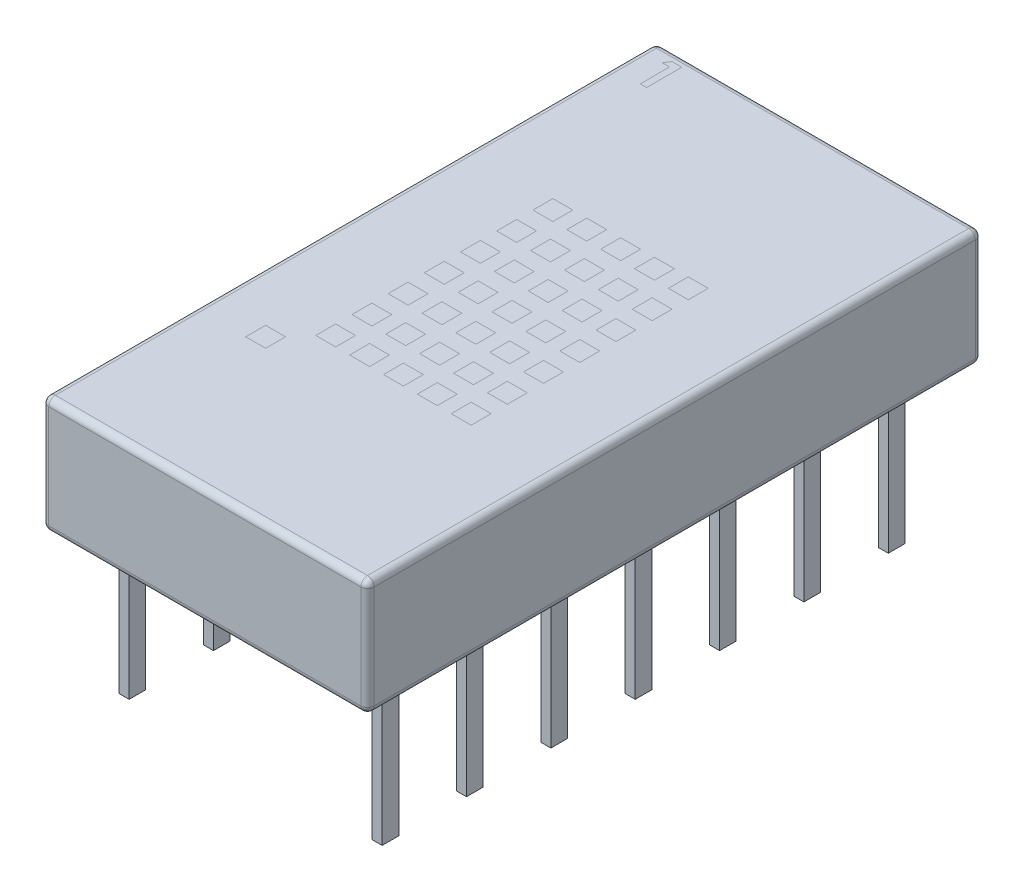
SolidWorks part; units mm, degrees
ref_plane "Front Plane" through (0, 0, 0) normal (0, 0, 1) x (1, 0, 0)
ref_plane "Top Plane" through (0, 0, 0) normal (0, 1, 0) x (1, 0, 0)
ref_plane "Right Plane" through (0, 0, 0) normal (1, 0, 0) x (0, 0, -1)
sketch "Sketch1" plane through (0, 0, 0) normal (0, 1, 0) x (1, 0, 0)
  line L1 (4.9, -9.25) -> (-4.9, -9.25)
  line L2 (4.9, -9.25) -> (4.9, 9.25)
  line L3 (4.9, 9.25) -> (-4.9, 9.25)
  line L4 (-4.9, -9.25) -> (-4.9, 9.25)
  line L5 (4.9, -9.25) -> (-4.9, 9.25) construction
  line L6 (4.9, 9.25) -> (-4.9, -9.25) construction
  point P0 (0, 0)
  dimension "D1" = 9.8
  dimension "D2" = 18.5
extrude "Boss-Extrude1" add sketch "Sketch1" along normal blind 3.5
sketch "Sketch2" plane through (0, 3.5, 0) normal (0, 1, 0) x (1, 0, 0)
  line L0 (0, 9.25) -> (0, 0) construction
  line L1 (4.9, 9.25) -> (-4.9, 9.25) construction
  line L2 (0, 0) -> (4.9, 0) construction
  line L3 (4.9, -9.25) -> (4.9, 9.25) construction
  line L4 (-1.32, 3.57) -> (-0.72, 3.57)
  line L5 (-2.34, 3.57) -> (-1.74, 3.57)
  line L6 (-2.34, 3.57) -> (-2.34, 2.97)
  line L7 (-2.34, 2.97) -> (-1.74, 2.97)
  line L8 (-1.74, 3.57) -> (-1.74, 2.97)
  line L9 (-2.34, 3.57) -> (-1.74, 2.97) construction
  line L10 (-2.34, 2.97) -> (-1.74, 3.57) construction
  line L11 (-0.72, 3.57) -> (-0.72, 2.97)
  line L12 (-1.32, 2.97) -> (-0.72, 2.97)
  line L13 (-1.32, 3.57) -> (-1.32, 2.97)
  line L14 (-0.3, 3.57) -> (0.3, 3.57)
  line L15 (0.3, 3.57) -> (0.3, 2.97)
  line L16 (-0.3, 2.97) -> (0.3, 2.97)
  line L17 (-0.3, 3.57) -> (-0.3, 2.97)
  line L18 (0.72, 3.57) -> (1.32, 3.57)
  line L19 (1.32, 3.57) -> (1.32, 2.97)
  line L20 (0.72, 2.97) -> (1.32, 2.97)
  line L21 (0.72, 3.57) -> (0.72, 2.97)
  line L22 (1.74, 3.57) -> (2.34, 3.57)
  line L23 (2.34, 3.57) -> (2.34, 2.97)
  line L24 (1.74, 2.97) -> (2.34, 2.97)
  line L25 (1.74, 3.57) -> (1.74, 2.97)
  line L26 (-1.32, 2.48) -> (-0.72, 2.48)
  line L27 (-0.72, 2.48) -> (-0.72, 1.88)
  line L28 (-1.32, 1.88) -> (-0.72, 1.88)
  line L29 (-1.32, 2.48) -> (-1.32, 1.88)
  line L30 (-0.3, 2.48) -> (0.3, 2.48)
  line L31 (0.3, 2.48) -> (0.3, 1.88)
  line L32 (-0.3, 1.88) -> (0.3, 1.88)
  line L33 (-0.3, 2.48) -> (-0.3, 1.88)
  line L34 (0.72, 2.48) -> (1.32, 2.48)
  line L35 (1.32, 2.48) -> (1.32, 1.88)
  line L36 (0.72, 1.88) -> (1.32, 1.88)
  line L37 (0.72, 2.48) -> (0.72, 1.88)
  line L38 (1.74, 2.48) -> (2.34, 2.48)
  line L39 (2.34, 2.48) -> (2.34, 1.88)
  line L40 (1.74, 1.88) -> (2.34, 1.88)
  line L41 (1.74, 2.48) -> (1.74, 1.88)
  line L42 (-1.32, 1.39) -> (-0.72, 1.39)
  line L43 (-0.72, 1.39) -> (-0.72, 0.79)
  line L44 (-1.32, 0.79) -> (-0.72, 0.79)
  line L45 (-1.32, 1.39) -> (-1.32, 0.79)
  line L46 (-0.3, 1.39) -> (0.3, 1.39)
  line L47 (0.3, 1.39) -> (0.3, 0.79)
  line L48 (-0.3, 0.79) -> (0.3, 0.79)
  line L49 (-0.3, 1.39) -> (-0.3, 0.79)
  line L50 (0.72, 1.39) -> (1.32, 1.39)
  line L51 (1.32, 1.39) -> (1.32, 0.79)
  line L52 (0.72, 0.79) -> (1.32, 0.79)
  line L53 (0.72, 1.39) -> (0.72, 0.79)
  line L54 (1.74, 1.39) -> (2.34, 1.39)
  line L55 (2.34, 1.39) -> (2.34, 0.79)
  line L56 (1.74, 0.79) -> (2.34, 0.79)
  line L57 (1.74, 1.39) -> (1.74, 0.79)
  line L58 (-1.32, 0.3) -> (-0.72, 0.3)
  line L59 (-0.72, 0.3) -> (-0.72, -0.3)
  line L60 (-1.32, -0.3) -> (-0.72, -0.3)
  line L61 (-1.32, 0.3) -> (-1.32, -0.3)
  line L62 (-0.3, 0.3) -> (0.3, 0.3)
  line L63 (0.3, 0.3) -> (0.3, -0.3)
  line L64 (-0.3, -0.3) -> (0.3, -0.3)
  line L65 (-0.3, 0.3) -> (-0.3, -0.3)
  line L66 (0.72, 0.3) -> (1.32, 0.3)
  line L67 (1.32, 0.3) -> (1.32, -0.3)
  line L68 (0.72, -0.3) -> (1.32, -0.3)
  line L69 (0.72, 0.3) -> (0.72, -0.3)
  line L70 (1.74, 0.3) -> (2.34, 0.3)
  line L71 (2.34, 0.3) -> (2.34, -0.3)
  line L72 (1.74, -0.3) -> (2.34, -0.3)
  line L73 (1.74, 0.3) -> (1.74, -0.3)
  line L74 (-1.32, -0.79) -> (-0.72, -0.79)
  line L75 (-0.72, -0.79) -> (-0.72, -1.39)
  line L76 (-1.32, -1.39) -> (-0.72, -1.39)
  line L77 (-1.32, -0.79) -> (-1.32, -1.39)
  line L78 (-0.3, -0.79) -> (0.3, -0.79)
  line L79 (0.3, -0.79) -> (0.3, -1.39)
  line L80 (-0.3, -1.39) -> (0.3, -1.39)
  line L81 (-0.3, -0.79) -> (-0.3, -1.39)
  line L82 (0.72, -0.79) -> (1.32, -0.79)
  line L83 (1.32, -0.79) -> (1.32, -1.39)
  line L84 (0.72, -1.39) -> (1.32, -1.39)
  line L85 (0.72, -0.79) -> (0.72, -1.39)
  line L86 (1.74, -0.79) -> (2.34, -0.79)
  line L87 (2.34, -0.79) -> (2.34, -1.39)
  line L88 (1.74, -1.39) -> (2.34, -1.39)
  line L89 (1.74, -0.79) -> (1.74, -1.39)
  line L90 (-1.32, -1.88) -> (-0.72, -1.88)
  line L91 (-0.72, -1.88) -> (-0.72, -2.48)
  line L92 (-1.32, -2.48) -> (-0.72, -2.48)
  line L93 (-1.32, -1.88) -> (-1.32, -2.48)
  line L94 (-0.3, -1.88) -> (0.3, -1.88)
  line L95 (0.3, -1.88) -> (0.3, -2.48)
  line L96 (-0.3, -2.48) -> (0.3, -2.48)
  line L97 (-0.3, -1.88) -> (-0.3, -2.48)
  line L98 (0.72, -1.88) -> (1.32, -1.88)
  line L99 (1.32, -1.88) -> (1.32, -2.48)
  line L100 (0.72, -2.48) -> (1.32, -2.48)
  line L101 (0.72, -1.88) -> (0.72, -2.48)
  line L102 (1.74, -1.88) -> (2.34, -1.88)
  line L103 (2.34, -1.88) -> (2.34, -2.48)
  line L104 (1.74, -2.48) -> (2.34, -2.48)
  line L105 (1.74, -1.88) -> (1.74, -2.48)
  line L106 (-1.32, -2.97) -> (-0.72, -2.97)
  line L107 (-0.72, -2.97) -> (-0.72, -3.57)
  line L108 (-1.32, -3.57) -> (-0.72, -3.57)
  line L109 (-1.32, -2.97) -> (-1.32, -3.57)
  line L110 (-0.3, -2.97) -> (0.3, -2.97)
  line L111 (0.3, -2.97) -> (0.3, -3.57)
  line L112 (-0.3, -3.57) -> (0.3, -3.57)
  line L113 (-0.3, -2.97) -> (-0.3, -3.57)
  line L114 (0.72, -2.97) -> (1.32, -2.97)
  line L115 (1.32, -2.97) -> (1.32, -3.57)
  line L116 (0.72, -3.57) -> (1.32, -3.57)
  line L117 (0.72, -2.97) -> (0.72, -3.57)
  line L118 (1.74, -2.97) -> (2.34, -2.97)
  line L119 (2.34, -2.97) -> (2.34, -3.57)
  line L120 (1.74, -3.57) -> (2.34, -3.57)
  line L121 (1.74, -2.97) -> (1.74, -3.57)
  line L122 (-2.34, 2.48) -> (-1.74, 2.48)
  line L123 (-1.74, 2.48) -> (-1.74, 1.88)
  line L124 (-2.34, 1.88) -> (-1.74, 1.88)
  line L125 (-2.34, 2.48) -> (-2.34, 1.88)
  line L126 (-2.34, 1.39) -> (-1.74, 1.39)
  line L127 (-1.74, 1.39) -> (-1.74, 0.79)
  line L128 (-2.34, 0.79) -> (-1.74, 0.79)
  line L129 (-2.34, 1.39) -> (-2.34, 0.79)
  line L130 (-2.34, 0.3) -> (-1.74, 0.3)
  line L131 (-1.74, 0.3) -> (-1.74, -0.3)
  line L132 (-2.34, -0.3) -> (-1.74, -0.3)
  line L133 (-2.34, 0.3) -> (-2.34, -0.3)
  line L134 (-2.34, -0.79) -> (-1.74, -0.79)
  line L135 (-1.74, -0.79) -> (-1.74, -1.39)
  line L136 (-2.34, -1.39) -> (-1.74, -1.39)
  line L137 (-2.34, -0.79) -> (-2.34, -1.39)
  line L138 (-2.34, -1.88) -> (-1.74, -1.88)
  line L139 (-1.74, -1.88) -> (-1.74, -2.48)
  line L140 (-2.34, -2.48) -> (-1.74, -2.48)
  line L141 (-2.34, -1.88) -> (-2.34, -2.48)
  line L142 (-2.34, -2.97) -> (-1.74, -2.97)
  line L143 (-1.74, -2.97) -> (-1.74, -3.57)
  line L144 (-2.34, -3.57) -> (-1.74, -3.57)
  line L145 (-2.34, -2.97) -> (-2.34, -3.57)
  line L146 (-2.34, 3.57) -> (-1.32, 3.57) construction
  line L147 (-2.34, 3.57) -> (-2.34, 2.48) construction
  line L148 (-0.3, 0.3) -> (0.3, -0.3) construction
  line L149 (-1.74, -2.97) -> (-1.32, -2.97) construction
  line L150 (-3.36, -4.06) -> (-2.76, -4.06)
  line L151 (-3.36, -4.06) -> (-3.36, -4.66)
  line L152 (-3.36, -4.66) -> (-2.76, -4.66)
  line L153 (-2.76, -4.06) -> (-2.76, -4.66)
  line L154 (-3.36, -4.06) -> (-2.76, -4.66) construction
  line L155 (-3.36, -4.66) -> (-2.76, -4.06) construction
  line L156 (-1.74, -2.48) -> (-1.74, -2.97) construction
  line L157 (-2.34, -3.57) -> (-2.34, -4.06) construction
  line L158 (-2.34, -4.06) -> (-2.76, -4.06) construction
  text T0 "<b>1</b>" font "Century Gothic" height in points 4
  point P5 (-2.04, 3.27)
  point P13 (0, 0)
  point P14 (-3.06, -4.36)
  dimension "D1" = 0.6
  dimension "D2" = 0.6
  dimension "D5" = 90
  dimension "D6" = 1.02
  dimension "D7" = 1.09
  dimension "D3" = 5
  dimension "D4" = 7
wrap "Wrap1" sketch "Sketch2" wrap type scribe source sketch "Sketch2"
sketch "Sketch3" plane through (0, 0, 0) normal (0, -1, 0) x (1, 0, 0)
  line L0 (3.96, -7.87) -> (3.96, -7.37)
  line L1 (-3.66, -7.87) -> (-3.96, -7.87)
  line L2 (-3.66, -7.87) -> (-3.66, -7.37)
  line L3 (-3.66, -7.37) -> (-3.96, -7.37)
  line L4 (-3.96, -7.87) -> (-3.96, -7.37)
  line L5 (-3.66, -7.87) -> (-3.96, -7.37) construction
  line L6 (-3.66, -7.37) -> (-3.96, -7.87) construction
  line L7 (3.96, -7.87) -> (3.66, -7.87)
  line L8 (3.66, -7.87) -> (3.66, -7.37)
  line L9 (3.96, -7.37) -> (3.66, -7.37)
  line L10 (3.96, -5.33) -> (3.96, -4.83)
  line L11 (3.96, -5.33) -> (3.66, -5.33)
  line L12 (3.66, -5.33) -> (3.66, -4.83)
  line L13 (3.96, -4.83) -> (3.66, -4.83)
  line L14 (3.96, -2.79) -> (3.96, -2.29)
  line L15 (3.96, -2.79) -> (3.66, -2.79)
  line L16 (3.66, -2.79) -> (3.66, -2.29)
  line L17 (3.96, -2.29) -> (3.66, -2.29)
  line L18 (3.96, -0.25) -> (3.96, 0.25)
  line L19 (3.96, -0.25) -> (3.66, -0.25)
  line L20 (3.66, -0.25) -> (3.66, 0.25)
  line L21 (3.96, 0.25) -> (3.66, 0.25)
  line L22 (3.96, 2.29) -> (3.96, 2.79)
  line L23 (3.96, 2.29) -> (3.66, 2.29)
  line L24 (3.66, 2.29) -> (3.66, 2.79)
  line L25 (3.96, 2.79) -> (3.66, 2.79)
  line L26 (3.96, 4.83) -> (3.96, 5.33)
  line L27 (3.96, 4.83) -> (3.66, 4.83)
  line L28 (3.66, 4.83) -> (3.66, 5.33)
  line L29 (3.96, 5.33) -> (3.66, 5.33)
  line L30 (3.96, 7.37) -> (3.96, 7.87)
  line L31 (3.96, 7.37) -> (3.66, 7.37)
  line L32 (3.66, 7.37) -> (3.66, 7.87)
  line L33 (3.96, 7.87) -> (3.66, 7.87)
  line L34 (-3.66, -5.33) -> (-3.66, -4.83)
  line L35 (-3.66, -5.33) -> (-3.96, -5.33)
  line L36 (-3.96, -5.33) -> (-3.96, -4.83)
  line L37 (-3.66, -4.83) -> (-3.96, -4.83)
  line L38 (-3.66, -2.79) -> (-3.66, -2.29)
  line L39 (-3.66, -2.79) -> (-3.96, -2.79)
  line L40 (-3.96, -2.79) -> (-3.96, -2.29)
  line L41 (-3.66, -2.29) -> (-3.96, -2.29)
  line L42 (-3.66, -0.25) -> (-3.66, 0.25)
  line L43 (-3.66, -0.25) -> (-3.96, -0.25)
  line L44 (-3.96, -0.25) -> (-3.96, 0.25)
  line L45 (-3.66, 0.25) -> (-3.96, 0.25)
  line L46 (-3.66, 2.29) -> (-3.66, 2.79)
  line L47 (-3.66, 2.29) -> (-3.96, 2.29)
  line L48 (-3.96, 2.29) -> (-3.96, 2.79)
  line L49 (-3.66, 2.79) -> (-3.96, 2.79)
  line L50 (-3.66, 4.83) -> (-3.66, 5.33)
  line L51 (-3.66, 4.83) -> (-3.96, 4.83)
  line L52 (-3.96, 4.83) -> (-3.96, 5.33)
  line L53 (-3.66, 5.33) -> (-3.96, 5.33)
  line L54 (-3.66, 7.37) -> (-3.66, 7.87)
  line L55 (-3.66, 7.37) -> (-3.96, 7.37)
  line L56 (-3.96, 7.37) -> (-3.96, 7.87)
  line L57 (-3.66, 7.87) -> (-3.96, 7.87)
  line L58 (-3.81, -7.62) -> (3.81, -7.62) construction
  line L59 (-3.81, -7.62) -> (-3.81, -5.08) construction
  line L60 (-3.81, 7.62) -> (3.81, -7.62) construction
  point P0 (-3.81, -7.62)
  point P6 (0, 0)
  point P8 (3.81, -7.62)
  point P13 (3.81, -5.08)
  point P18 (3.81, -2.54)
  point P23 (3.81, 0)
  point P28 (3.81, 2.54)
  point P33 (3.81, 5.08)
  point P38 (3.81, 7.62)
  point P43 (-3.81, -5.08)
  point P48 (-3.81, -2.54)
  point P53 (-3.81, 0)
  point P58 (-3.81, 2.54)
  point P63 (-3.81, 5.08)
  point P68 (-3.81, 7.62)
  dimension "D1" = 0.5
  dimension "D2" = 0.3
  dimension "D5" = 90
  dimension "D6" = 7.62
  dimension "D7" = 15.24
  dimension "D3" = 2
  dimension "D4" = 7
extrude "Boss-Extrude2" add sketch "Sketch3" along normal blind 8 from surface starting at face at (-3.06, 3.5, 4.36)
fillet "Fillet1" radius 0.2 12 edges at (-4.9, 0, 0) (-4.9, 1.75, 9.25) (0, 0, 9.25) (4.9, 1.75, 9.25) (4.9, 0, 0) (4.9, 1.75, -9.25) (-4.9, 1.75, -9.25) (0, 0, -9.25) (0, 3.5, -9.25) (4.9, 3.5, 0) (0, 3.5, 9.25) (-4.9, 3.5, 0)
equation "\"D2@Sketch2\"=\"D1@Sketch2\""
